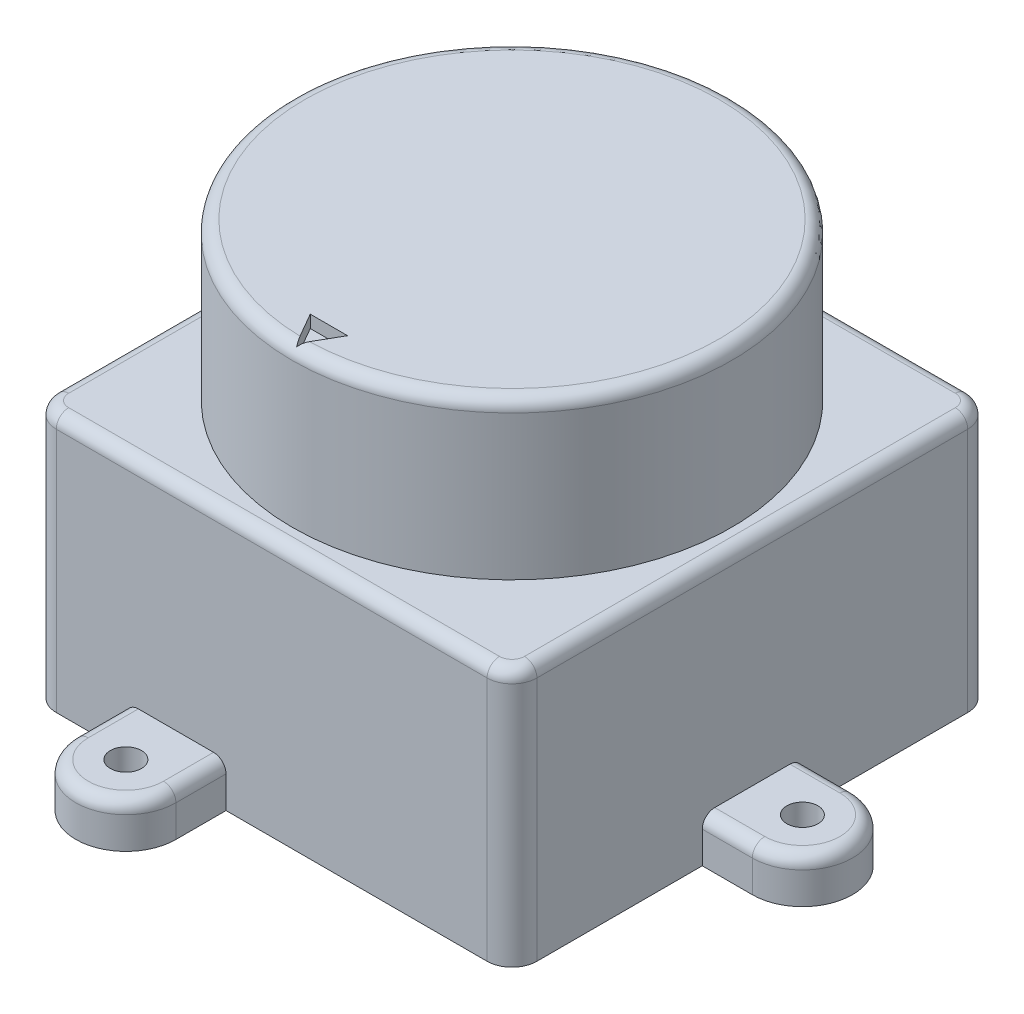
SolidWorks part; units mm, degrees
ref_plane "Front Plane" through (0, 0, 0) normal (0, 0, 1) x (1, 0, 0)
ref_plane "Top Plane" through (0, 0, 0) normal (0, 1, 0) x (1, 0, 0)
ref_plane "Right Plane" through (0, 0, 0) normal (1, 0, 0) x (0, 0, -1)
sketch "Sketch1" plane through (0, 0, 0) normal (0, 1, 0) x (1, 0, 0)
  line L1 (0, 0) -> (38.59, 0)
  line L2 (0, 0) -> (0, 38.59)
  line L3 (0, 38.59) -> (38.59, 38.59)
  line L4 (38.59, 0) -> (38.59, 38.59)
  dimension "D1" = 38.59
extrude "Boss-Extrude1" add sketch "Sketch1" along normal blind 20.7
draft "Draft1" [suppressed] type of draft neutral plane draft angle 2 faces to draft 4 reverse direction yes parameters "D1"=2
sketch "Sketch2" plane through (0, 20.7, 0) normal (0, 1, 0) x (1, 0, 0)
  line L0 (0, 38.59) -> (38.59, 0) construction
  circle A0 centre (19.295, 19.295) radius 17.645
  dimension "D1" = 35.29
extrude "Boss-Extrude2" add sketch "Sketch2" along normal blind 12.6
sketch "Sketch3" plane through (0, 33.3, 0) normal (0, 1, 0) x (1, 0, 0)
  line L0 (17.795, 4.5981) -> (19.295, 2)
  line L1 (19.295, 2) -> (20.795, 4.5981)
  line L2 (20.795, 4.5981) -> (17.795, 4.5981)
  line L3 (19.295, 38.59) -> (19.295, 2) construction
  line L4 (38.59, 38.59) -> (0, 38.59) construction
  line L5 (0, 0) -> (38.59, 0) construction
  dimension "D1" = 2
  dimension "D2" = 3
extrude "Cut-Extrude1" cut sketch "Sketch3" against normal blind 1
sketch "Sketch6" plane through (0, 0, 0) normal (1, 0, 0) x (0, 0, -1)
  line L0 (38.59, 0) -> (23.295, 1) construction
  line L1 (23.295, 5) -> (15.295, 5)
  line L2 (23.295, 5) -> (23.295, 1)
  line L3 (23.295, 1) -> (15.295, 1)
  line L4 (15.295, 5) -> (15.295, 1)
  line L5 (15.295, 1) -> (0, 0) construction
  line L6 (38.59, 0) -> (0, 0) construction
  dimension "D1" = 8
  dimension "D2" = 4
  dimension "D3" = 1
extrude "Cut-Extrude2" cut sketch "Sketch6" along normal blind 4
sketch "Sketch8" plane through (0, 0, 0) normal (0, -1, 0) x (1, 0, 0)
  line L0 (11.61, 4.02) -> (11.61, -42.61) construction
  line L1 (42.61, -19.295) -> (11.61, -19.295) construction
  line L2 (38.59, 0) -> (38.59, -38.59) construction
  line L3 (0, 0) -> (38.59, 0) construction
  line L4 (38.59, -38.59) -> (0, -38.59) construction
  line L5 (7.59, 4.02) -> (7.59, 0)
  line L6 (7.59, 0) -> (15.63, 0)
  line L7 (15.63, 0) -> (15.63, 4.02)
  line L8 (42.61, -15.275) -> (38.59, -15.275)
  line L9 (38.59, -15.275) -> (38.59, -23.315)
  line L10 (38.59, -23.315) -> (42.61, -23.315)
  line L11 (7.59, -42.61) -> (7.59, -38.59)
  line L12 (7.59, -38.59) -> (15.63, -38.59)
  line L13 (15.63, -38.59) -> (15.63, -42.61)
  circle A0 centre (11.61, 4.02) radius 4.02
  circle A1 centre (11.61, -42.61) radius 4.02
  circle A2 centre (42.61, -19.295) radius 4.02
  circle A3 centre (11.61, 4.02) radius 1.25
  circle A4 centre (42.61, -19.295) radius 1.25
  circle A5 centre (11.61, -42.61) radius 1.25
  point P8 (38.59, -19.295)
  line M10 (0, -38.59) -> (38.59, -38.59)
  line M11 (38.59, -38.59) -> (38.59, 0)
  line M12 (38.59, 0) -> (0, 0)
  dimension "D1" = 31
  dimension "D3" = 2.5
  dimension "D2" = 46.63
extrude "Boss-Extrude3" add sketch "Sketch8" against normal blind 3.55 contours A0 L5 L6 | A0 L7 M12 | A0 A3 | A2 L8 L9 | A2 L10 M11 | A2 A4 | A1 L11 M10 | A1 A5 | A1 L13 L12 region at (8.4879, 0, 0.8979) region at (14.7321, 0, -39.4879) region at (39.4879, 0, -16.1729) region at (11.61, 0, 7.9263) region at (14.7321, 0, 0.8979) region at (45.3722, 0, -16.5328) region at (39.4879, 0, -22.4171) region at (8.4879, 0, -39.4879) region at (14.3722, 0, -39.8478)
fillet "Fillet2" radius 2 4 edges at (0, 10.35, -38.59) (38.59, 10.35, -38.59) (38.59, 10.35, 0) (0, 10.35, 0)
fillet "Fillet1" radius 1 18 edges at (7.59, 3.55, -40.6) (15.63, 3.55, -40.6) (40.6, 3.55, -23.315) (40.6, 3.55, -15.275) (15.63, 3.55, 2.01) (7.59, 3.55, 2.01) (11.61, 3.55, -46.63) (46.63, 3.55, -19.295) (11.61, 3.55, 8.04) (38.0042, 20.7, -38.0042) (38.59, 20.7, -19.295) (38.0042, 20.7, -0.5858) (19.295, 20.7, 0) (0.5858, 20.7, -0.5858) (0, 20.7, -19.295) (0.5858, 20.7, -38.0042) (19.295, 33.3, -1.65) (19.295, 20.7, -38.59)
